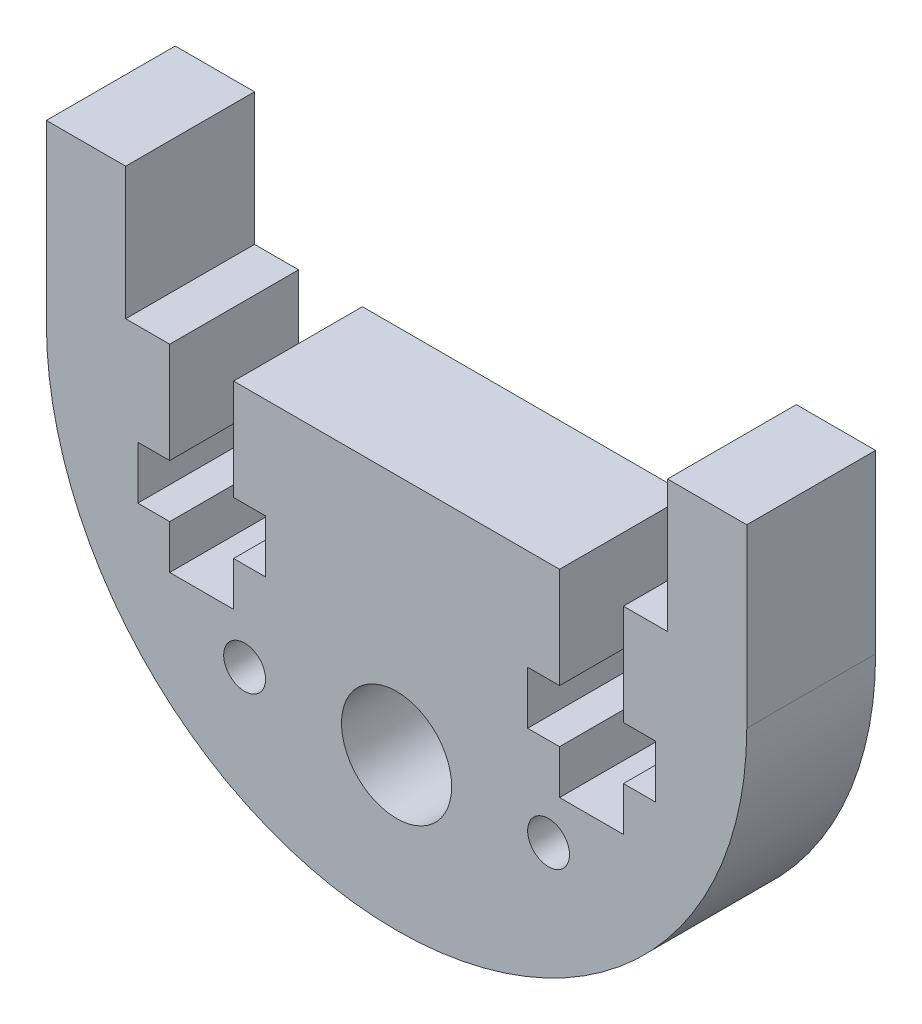
SolidWorks part; units mm, degrees
material "Acrylic (Medium-high impact)"
ref_plane "Front Plane" through (0, 0, 0) normal (0, 0, 1) x (1, 0, 0)
ref_plane "Top Plane" through (0, 0, 0) normal (0, 1, 0) x (1, 0, 0)
ref_plane "Right Plane" through (0, 0, 0) normal (1, 0, 0) x (0, 0, -1)
sketch "Model" plane through (0, 0, 0) normal (0, 0, 1) x (1, 0, 0)
  line L0 (546.1095, 558.5325) -> (553.5095, 558.5325)
  line L1 (553.5095, 547.5325) -> (553.5095, 540.8575) construction
  line L2 (553.5095, 547.5325) -> (553.5095, 540.8575) construction
  line L3 (546.6095, 547.5325) -> (553.5095, 547.5325) construction
  line L4 (560.4095, 547.5325) -> (553.5095, 547.5325) construction
  line L5 (553.5095, -443.4675) -> (553.5095, 49556.5325) construction
  line L6 (553.5095, 547.5325) -> (553.5095, 540.8575) construction
  line L7 (553.5095, 540.8575) -> (553.5095, 547.5325) construction
  line L8 (560.9095, 553.9566) -> (560.9095, 558.5325)
  line L9 (559.4595, 553.9566) -> (560.9095, 553.9566)
  line L10 (559.4595, 551.5565) -> (559.4595, 553.9566)
  line L11 (560.9095, 551.5565) -> (559.4595, 551.5565)
  line L12 (560.9095, 549.5565) -> (560.9095, 551.5565)
  line L13 (563.8095, 549.5565) -> (560.9095, 549.5565)
  line L14 (563.8095, 551.5565) -> (563.8095, 549.5565)
  line L15 (565.2595, 551.5565) -> (563.8095, 551.5565)
  line L16 (565.2595, 553.9566) -> (565.2595, 551.5565)
  line L17 (563.8095, 553.9566) -> (565.2595, 553.9566)
  line L18 (563.8095, 558.5325) -> (563.8095, 553.9566)
  line L19 (565.8095, 558.5325) -> (563.8095, 558.5325)
  line L20 (565.8095, 564.5325) -> (565.8095, 558.5325)
  line L21 (569.4095, 564.5325) -> (565.8095, 564.5325)
  line L22 (569.4095, 556.5325) -> (569.4095, 564.5325)
  line L23 (560.9095, 558.5325) -> (553.5095, 558.5325)
  line L24 (553.5095, 547.5325) -> (553.5095, 553.0893) construction
  line L25 (543.2095, 558.5325) -> (546.1095, 558.5325) construction
  line L26 (544.6595, 558.5325) -> (544.6595, 549.5565) construction
  line L27 (562.3595, 558.5325) -> (562.3595, 549.5565) construction
  line L28 (560.9095, 558.5325) -> (563.8095, 558.5325) construction
  line L41 (537.6095, 556.5325) -> (537.6095, 564.5325)
  line L42 (537.6095, 564.5325) -> (541.2095, 564.5325)
  line L43 (541.2095, 564.5325) -> (541.2095, 558.5325)
  line L44 (541.2095, 558.5325) -> (543.2095, 558.5325)
  line L45 (543.2095, 558.5325) -> (543.2095, 553.9566)
  line L46 (543.2095, 553.9566) -> (541.7595, 553.9566)
  line L47 (541.7595, 553.9566) -> (541.7595, 551.5565)
  line L48 (541.7595, 551.5565) -> (543.2095, 551.5565)
  line L49 (543.2095, 551.5565) -> (543.2095, 549.5565)
  line L50 (543.2095, 549.5565) -> (546.1095, 549.5565)
  line L51 (546.1095, 549.5565) -> (546.1095, 551.5565)
  line L52 (546.1095, 551.5565) -> (547.5595, 551.5565)
  line L53 (547.5595, 551.5565) -> (547.5595, 553.9566)
  line L54 (547.5595, 553.9566) -> (546.1095, 553.9566)
  line L55 (546.1095, 553.9566) -> (546.1095, 558.5325)
  circle A0 centre (546.6095, 547.5325) radius 0.95
  circle A1 centre (553.5095, 547.5325) radius 2.5
  arc A4 (569.4095, 556.5325) -> (537.6095, 556.5325) centre (553.5095, 556.5325) cw
  circle A8 centre (560.4095, 547.5325) radius 0.95
  point P7 (544.6595, 558.5325)
  dimension "D10" = 6.9
  dimension "D9" = 1.9
  dimension "D14" = 5
  dimension "D1" = 3.6
  dimension "D2" = 6
  dimension "D3" = 8
  dimension "D4" = 2.4001
  dimension "D5" = 1.45
  dimension "D6" = 4.5759
  dimension "D7" = 2
  dimension "D8" = 2
  dimension "D11" = 7.4
  dimension "D12" = 11
  dimension "D13" = 2.9
extrude "Boss-Extrude2" add sketch "Model" along normal blind 5.85 contours A4 L22 L21 L20 L19 L18 L17 L16 L15 L14 L13 L12 L11 L10 L9 L8 L23 L0 L55 L54 L53 L52 L51 L50 L49 L48 L47 L46 L45 L44 L43 L42 L41 A1 A0 A8 region at (553.5095, 551.7089, 0)
